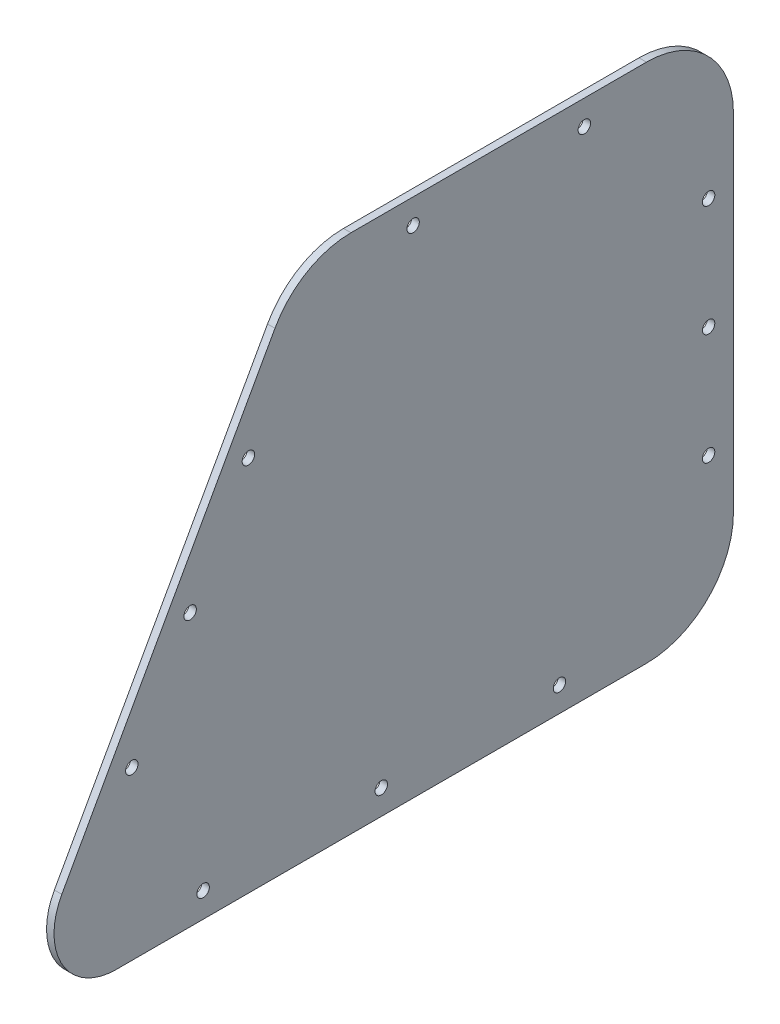
SolidWorks part; units mm, degrees
material "Acrylic (Medium-high impact)"
ref_plane "Front Plane" through (0, 0, 0) normal (0, 0, 1) x (1, 0, 0)
ref_plane "Top Plane" through (0, 0, 0) normal (0, 1, 0) x (1, 0, 0)
ref_plane "Right Plane" through (0, 0, 0) normal (1, 0, 0) x (0, 0, -1)
sketch "Sketch1" plane through (0, 0, 0) normal (1, 0, 0) x (0, 0, -1)
  line L0 (0, -1000) -> (0, 49000) construction
  line L1 (-1000, 0) -> (49000, 0) construction
  line L14 (-12.1885, 179.5) -> (106.6837, 179.5) construction
  line L15 (-29.6717, 169.2129) -> (-115.4252, 14.8564) construction
  line L16 (-106.6837, 0) -> (106.6837, 0) construction
  line L17 (126.6837, 20) -> (126.6837, 159.5) construction
  line L18 (-12.1885, 194.5) -> (106.6837, 194.5)
  line L19 (141.6837, 20) -> (141.6837, 159.5)
  line L20 (-106.6837, -15) -> (106.6837, -15)
  line L21 (-42.784, 176.4975) -> (-128.5376, 22.1411)
  arc A12 (-106.6837, 0) -> (-115.4252, 14.8564) centre (-106.6837, 10) cw construction
  arc A13 (106.6837, 0) -> (126.6837, 20) centre (106.6837, 20) ccw construction
  arc A14 (126.6837, 159.5) -> (106.6837, 179.5) centre (106.6837, 159.5) ccw construction
  arc A16 (-29.6717, 169.2129) -> (-12.1885, 179.5) centre (-12.1885, 159.5) cw construction
  arc A17 (141.6837, 159.5) -> (106.6837, 194.5) centre (106.6837, 159.5) ccw
  arc A18 (106.6837, -15) -> (141.6837, 20) centre (106.6837, 20) ccw
  arc A19 (-106.6837, -15) -> (-128.5376, 22.1411) centre (-106.6837, 10) cw
  arc A20 (-42.784, 176.4975) -> (-12.1885, 194.5) centre (-12.1885, 159.5) cw
  point P17 (47.2476, 179.5)
  point P18 (0, 0)
  dimension "D2" = 20
  dimension "D3" = 20
  dimension "D5" = 79.4361
  dimension "D1" = 10
  dimension "D4" = 20
  dimension "D6" = 213.3673
  dimension "D7" = 179.5
  dimension "D8" = 15
extrude "Boss-Extrude1" add sketch "Sketch1" along normal blind 3
sketch "Sketch2" plane through (3, 0, 0) normal (1, 0, 0) x (0, 0, -1)
  line L4 (-34.0424, 171.6411) -> (-119.796, 17.2846)
  line L5 (-34.0424, 171.6411) -> (-119.796, 17.2846) construction
  line L6 (-106.6837, -5) -> (106.6837, -5)
  line L7 (-106.6837, -5) -> (106.6837, -5) construction
  line L8 (131.6837, 20) -> (131.6837, 159.5)
  line L9 (131.6837, 20) -> (131.6837, 159.5) construction
  line L10 (106.6837, 184.5) -> (-12.1885, 184.5)
  line L11 (106.6837, 184.5) -> (-12.1885, 184.5) construction
  arc A4 (-12.1885, 184.5) -> (-34.0424, 171.6411) centre (-12.1885, 159.5) ccw
  arc A5 (-12.1885, 184.5) -> (-34.0424, 171.6411) centre (-12.1885, 159.5) ccw construction
  arc A6 (-119.796, 17.2846) -> (-106.6837, -5) centre (-106.6837, 10) ccw
  arc A7 (-119.796, 17.2846) -> (-106.6837, -5) centre (-106.6837, 10) ccw construction
  arc A8 (106.6837, -5) -> (131.6837, 20) centre (106.6837, 20) ccw
  arc A9 (106.6837, -5) -> (131.6837, 20) centre (106.6837, 20) ccw construction
  arc A10 (131.6837, 159.5) -> (106.6837, 184.5) centre (106.6837, 159.5) ccw
  arc A11 (131.6837, 159.5) -> (106.6837, 184.5) centre (106.6837, 159.5) ccw construction
  circle A32 centre (81.6837, 184.5) radius 2.5
  circle A33 centre (12.8115, 184.5) radius 2.5
  circle A34 centre (131.6837, 134.5) radius 2.5
  circle A35 centre (131.6837, 89.75) radius 2.5
  circle A44 centre (131.6837, 44.9999) radius 2.5
  circle A45 centre (71.6837, -5) radius 2.5
  circle A46 centre (0, -5) radius 2.5
  circle A47 centre (-71.6837, -5) radius 2.5
  circle A48 centre (-100.3703, 52.2509) radius 2.5
  circle A49 centre (-76.9192, 94.4629) radius 2.5
  circle A50 centre (-53.4682, 136.6748) radius 2.5
  dimension "D4" = 25
  dimension "D6" = 24.9999
  dimension "D7" = 35
  dimension "D8" = 35
  dimension "D9" = 40
  dimension "D10" = 40
  dimension "D2" = 5
  dimension "D5" = 25
  dimension "D3" = 25
  dimension "D1" = 10
extrude "Cut-Extrude1" cut sketch "Sketch2" against normal up to next
